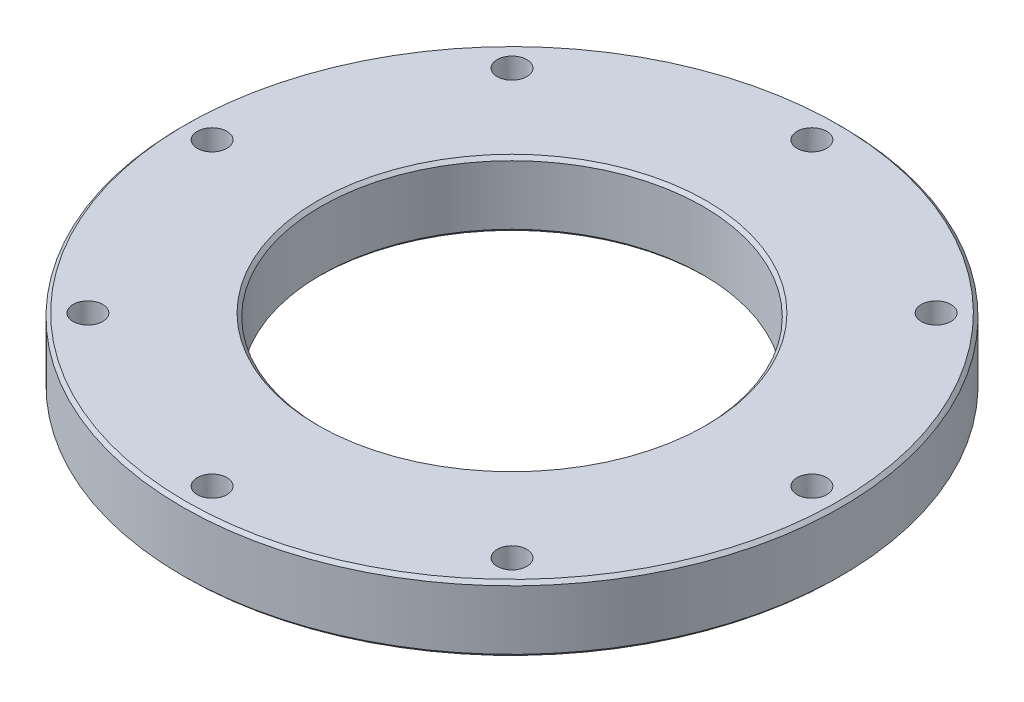
SolidWorks part; units mm, degrees
material "6061 Alloy"
ref_plane "Płaszczyzna przednia" through (0, 0, 0) normal (0, 0, 1) x (1, 0, 0)
ref_plane "Płaszczyzna górna" through (0, 0, 0) normal (0, 1, 0) x (1, 0, 0)
ref_plane "Płaszczyzna prawa" through (0, 0, 0) normal (1, 0, 0) x (0, 0, -1)
sketch "Sketch1" plane through (0, 0, 0) normal (0, 1, 0) x (1, 0, 0)
  circle A0 centre (0, 0) radius 50
  circle A1 centre (0, 0) radius 45.5 construction
  circle A2 centre (0, 45.5) radius 2.25
  circle A3 centre (32.1734, 32.1734) radius 2.25
  circle A4 centre (45.5, 0) radius 2.25
  circle A5 centre (32.1734, -32.1734) radius 2.25
  circle A6 centre (0, -45.5) radius 2.25
  circle A7 centre (-32.1734, -32.1734) radius 2.25
  circle A8 centre (-45.5, 0) radius 2.25
  circle A9 centre (-32.1734, 32.1734) radius 2.25
  circle A10 centre (0, 0) radius 29
  point P22 (0, 0)
  dimension "D1" = 100
  dimension "D2" = 91
  dimension "D3" = 4.5
  dimension "D5" = 58
  dimension "D4" = 8
extrude "Boss-Extrude1" add sketch "Sketch1" along normal blind 10
chamfer "Chamfer1" distance 0.5 angle 45 4 edges at (0, 10, 29) (0, 0, 29) (0, 10, 50) (0, 0, 50)
sketch "Sketch2" plane through (0, 0, 0) normal (0, 0, 1) x (1, 0, 0)
  line L0 (50, 0.5) -> (-50, 0.5) construction
  line L1 (-50, 9.5) -> (50, 9.5) construction
  line L2 (50, 0.5) -> (-50, 0.5)
  line L3 (-50, 9.5) -> (50, 9.5)
  line L4 (0, 9.5) -> (0, 0.5)
  point P6 (0, 5)
ref_axis "Axis1" through (0, 5, 0) along (0, 0, 1)
